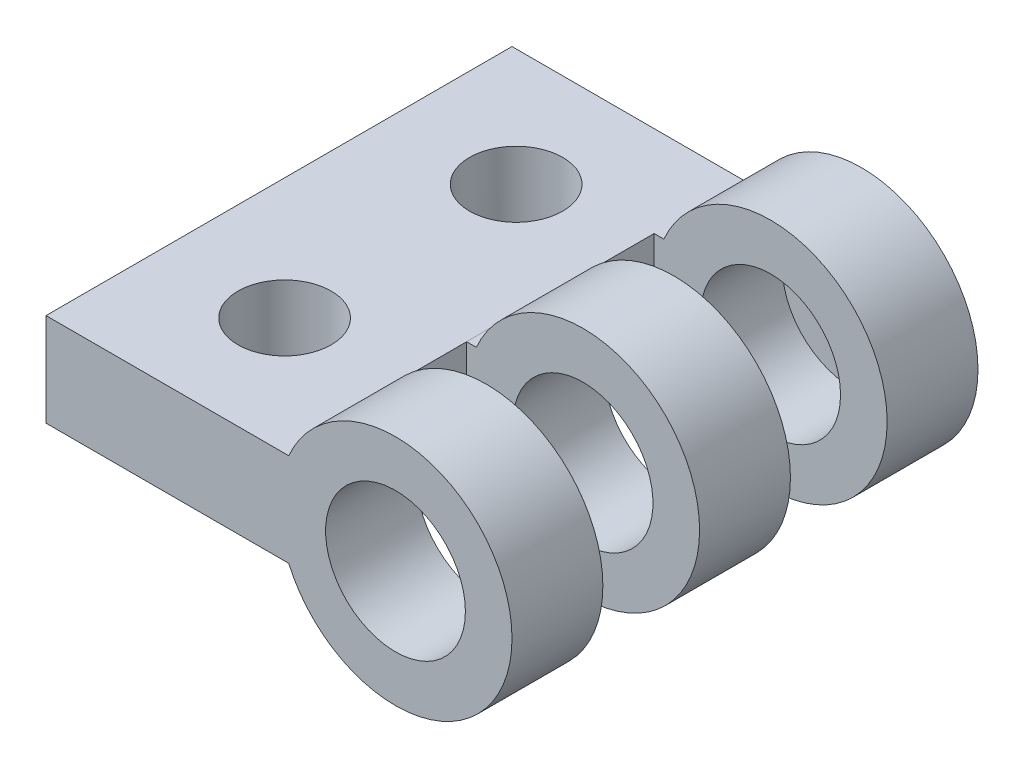
SolidWorks part; units mm, degrees
ref_plane "Front Plane" through (0, 0, 0) normal (0, 0, 1) x (1, 0, 0)
ref_plane "Top Plane" through (0, 0, 0) normal (0, 1, 0) x (1, 0, 0)
ref_plane "Right Plane" through (0, 0, 0) normal (1, 0, 0) x (0, 0, -1)
sketch "Sketch1" plane through (0, 0, 0) normal (0, 0, 1) x (1, 0, 0)
  circle A0 centre (0, 0) radius 2.5
  circle A1 centre (0, 0) radius 1.5
  dimension "D1" = 5
  dimension "D2" = 3
extrude "Boss-Extrude2" add sketch "Sketch1" along normal blind 1.95
sketch "Sketch6" plane through (0, 0, 0) normal (1, 0, 0) x (0, 0, -1)
  line L0 (0.3584, 2.6698) -> (0.3584, -2.6698) construction
  point P3 (0.3584, 0)
sketch "Sketch7" plane through (0, 0, 0) normal (0, 1, 0) x (1, 0, 0)
  line L0 (1.5, 0) -> (-1.5, 0) construction
  line L1 (-7.5, 0) -> (-2.5, 0)
  line L2 (-7.5, 0) -> (-7.5, -10)
  line L3 (-7.5, -10) -> (-2.5, -10)
  line L4 (-2.5, 0) -> (-2.5, -10)
  line L5 (-2.5, 0) -> (-2.5, -1.95) construction
  dimension "D1" = 10
  dimension "D2" = 0
  dimension "D3" = 0
  dimension "D4" = 5
extrude "Boss-Extrude3" add sketch "Sketch7" along normal blind 1 and the other way blind 1 separate body
sketch "Sketch8" plane through (-2.5, 0, 0) normal (1, 0, 0) x (0, 0, -1)
  line L0 (-1.95, -1) -> (-1.95, 1)
  line L1 (-1.95, 2.5) -> (-1.95, -2.5) construction
  line L2 (-10, -1) -> (0, -1) construction
  line L3 (-10, 1) -> (0, 1) construction
  line L4 (-1.95, 1) -> (0, 1)
  line L5 (0, 1) -> (0, -1)
  line L6 (0, -1) -> (-1.95, -1)
extrude "Boss-Extrude4" add sketch "Sketch8" along normal up to surface (0.2087 mm away) up to face at (2.5, 0, 0)
sketch "Sketch9" plane through (-2.5, 0, 0) normal (1, 0, 0) x (0, 0, -1)
  line L0 (-10, 0) -> (0, 0) construction
  line L1 (-10, -1) -> (-10, 1) construction
sketch "Sketch10" plane through (0, 0, 10) normal (0, 0, 1) x (1, 0, 0)
  circle A0 centre (0, 0) radius 2.5
  circle A1 centre (0, 0) radius 1.5
extrude "Boss-Extrude5" add sketch "Sketch10" against normal blind 1.95 separate body
sketch "Sketch11" plane through (-2.5, 0, 0) normal (1, 0, 0) x (0, 0, -1)
  line L0 (-5, -3.7452) -> (-5, 3.7452) construction
  point P3 (-5, 0)
ref_plane "Plane1" through (0, 0, 5) normal (0, 0, -1) x (0, 1, 0)
sketch "Sketch12" plane through (0, 0, 5) normal (0, 0, -1) x (0, 1, 0)
  circle A0 centre (0, 0) radius 2.5
  circle A1 centre (0, 0) radius 1.5
extrude "Boss-Extrude6" add sketch "Sketch12" along normal blind 0.975 and the other way blind 0.975 separate body
sketch "Sketch13" plane through (-2.5, 0, 0) normal (1, 0, 0) x (0, 0, -1)
  line L0 (-5.975, 2.5) -> (-5.975, -2.5) construction
  line L1 (-5.975, 1.0029) -> (-4.025, 1.0029)
  line L2 (-5.975, 1.0029) -> (-5.975, -1)
  line L3 (-5.975, -1) -> (-4.025, -1)
  line L4 (-4.025, 1.0029) -> (-4.025, -1)
  line L5 (-10, -1) -> (-1.95, -1) construction
  line L6 (-4.025, -2.5) -> (-4.025, 2.5) construction
  line L7 (-8.05, -2.5) -> (-8.05, 2.5) construction
  line L8 (-8.05, 1) -> (-10, 1)
  line L9 (-8.05, 1) -> (-8.05, -1)
  line L10 (-8.05, -1) -> (-10, -1)
  line L11 (-10, 1) -> (-10, -1)
  line L12 (-10, 1) -> (-1.95, 1) construction
  line L13 (-10, 2.5) -> (-10, -2.5) construction
extrude "Boss-Extrude7" add sketch "Sketch13" along normal up to surface (0.21 mm away) up to face at (2.5, 0, 8.05)
sketch "Sketch14" plane through (0, -1, 0) normal (0, -1, 0) x (-1, 0, 0)
  line L2 (2.5, -8.05) -> (2.5, -5.975) construction
  line L3 (2.5, -4.025) -> (2.5, -1.95) construction
  line L5 (2.5, -7.0125) -> (7.5, -7.0125) construction
  line L7 (7.5, 0) -> (7.5, -10) construction
sketch "Sketch15" plane through (0, 0, 0) normal (0, 0, -1) x (-1, 0, 0)
  circle A0 centre (0, 0) radius 1.5
extrude "Boss-Extrude8" add sketch "Sketch15" against normal blind 0.2
sketch "Sketch16" plane through (0, 1, 0) normal (0, 1, 0) x (1, 0, 0)
  line L0 (-4.8956, -10) -> (-4.8956, -4.9684) construction
  line L3 (-7.5, -10) -> (-2.2913, -10) construction
  line L4 (1.6775, -5) -> (-1.6775, -5) construction
  circle A0 centre (-4.8956, -7.4842) radius 1
  circle A1 centre (-4.8956, -2.5158) radius 1
  dimension "D1" = 2
extrude "Cut-Extrude1" cut sketch "Sketch16" against normal blind 10
